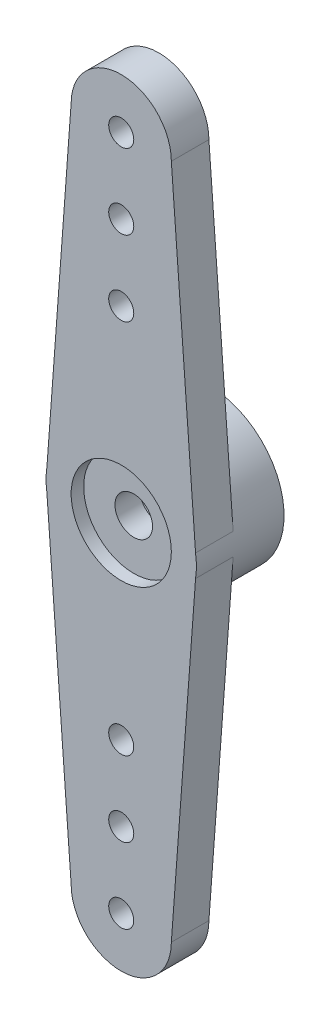
SolidWorks part; units mm, degrees
ref_plane "Plan de face" through (0, 0, 0) normal (0, 0, 1) x (1, 0, 0)
ref_plane "Plan de dessus" through (0, 0, 0) normal (0, 1, 0) x (1, 0, 0)
ref_plane "Plan de droite" through (0, 0, 0) normal (1, 0, 0) x (0, 0, -1)
sketch "Esquisse1" plane through (0, 0, 0) normal (0, 0, 1) x (1, 0, 0)
  line L0 (0, 0) -> (0, 15.5) construction
  line L1 (2, 13.5) -> (2.9673, 0.442)
  line L2 (-2, 13.5) -> (-2.9673, 0.442)
  line L3 (-15.6661, 0) -> (13.91, 0) construction
  line L4 (2, -13.5) -> (2.9673, -0.442)
  line L5 (-2, -13.5) -> (-2.9673, -0.442)
  arc A0 (-2.9673, 0.442) -> (-2.9673, -0.442) centre (0, 0) ccw
  arc A1 (2, 13.5) -> (-2, 13.5) centre (0, 13.5) ccw
  arc A2 (2, -13.5) -> (-2, -13.5) centre (0, -13.5) cw
  arc A3 (2.9673, -0.442) -> (2.9673, 0.442) centre (0, 0) ccw
  dimension "D1" = 6
  dimension "D2" = 4
  dimension "D3" = 13.5
  dimension "D4" = 13.058
  dimension "D5" = 13.058
  dimension "D6" = 13.058
  dimension "D7" = 13.058
extrude "Boss.-Extru.2" add sketch "Esquisse1" along normal blind 1.5
sketch "Esquisse2" plane through (0, 0, 0) normal (0, 0, -1) x (-1, 0, 0)
  circle A0 centre (0, 0) radius 3
  circle A1 centre (0, 0) radius 2
  dimension "D1" = 6
  dimension "D2" = 1
extrude "Boss.-Extru.3" add sketch "Esquisse2" along normal blind 2
sketch "Esquisse3" plane through (0, 0, 0) normal (0, 0, -1) x (-1, 0, 0)
  circle A0 centre (0, 0) radius 0.75
  dimension "D1" = 1.5
extrude "Enlèv. mat.-Extru.1" cut sketch "Esquisse3" against normal blind 2
sketch "Esquisse4" plane through (0, 0, 1.5) normal (0, 0, 1) x (1, 0, 0)
  circle A0 centre (0, 0) radius 2
  dimension "D1" = 4
extrude "Enlèv. mat.-Extru.2" cut sketch "Esquisse4" against normal blind 0.5
sketch "Esquisse5" plane through (0, 0, 1.5) normal (0, 0, 1) x (1, 0, 0)
  line L0 (0, -16.2626) -> (0, 16.9239) construction
  circle A0 centre (0, 13.5) radius 0.5
  dimension "D1" = 1
extrude "Enlèv. mat.-Extru.3" cut sketch "Esquisse5" against normal through all
pattern_linear "Répétition linéaire1" count 3 spacing 3 along (0, -1, 0) of "Enlèv. mat.-Extru.3"
mirror "Symétrie1" about plane through (0, 0, 0) normal (0, 1, 0) of "Répétition linéaire1"
